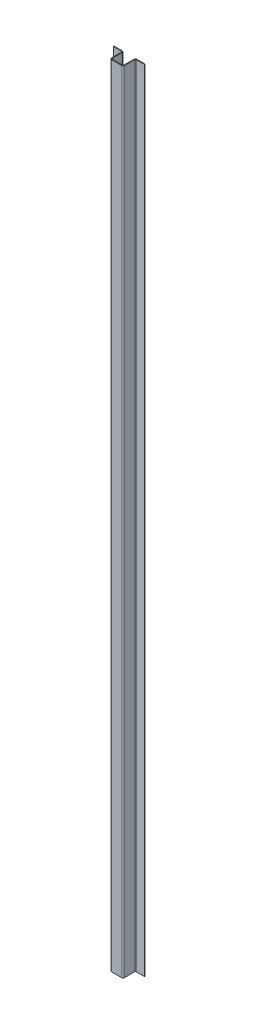
SolidWorks part; units mm, degrees
note: The reader was unsure of these and kept them because the rebuilt part matched: flange length of "Edge-Flange1", "Edge-Flange2".
material "Galvanized Steel"
ref_plane "Front Plane" through (0, 0, 0) normal (0, 0, 1) x (1, 0, 0)
ref_plane "Top Plane" through (0, 0, 0) normal (0, 1, 0) x (1, 0, 0)
ref_plane "Right Plane" through (0, 0, 0) normal (1, 0, 0) x (0, 0, -1)
sketch "Sketch1" plane through (0, 0, 0) normal (0, 0, 1) x (1, 0, 0)
  line L1 (20, -1214) -> (-20, -1214)
  line L2 (20, -1214) -> (20, 1214)
  line L3 (20, 1214) -> (-20, 1214)
  line L4 (-20, -1214) -> (-20, 1214)
  line L5 (20, -1214) -> (-20, 1214) construction
  line L6 (20, 1214) -> (-20, -1214) construction
  point P0 (0, 0)
  dimension "D1" = 2428
  dimension "D2" = 40
base flange "Base-Flange1" sketch "Sketch1" thickness 2 reverse thickness direction no parameters "D1"=8
edge flange "Edge-Flange1" sketch "Sketch10" flange profiles "Sketch10", "Sketch11" flange angle 90 flange length 40 flange position material inside bend radius 2.5 thickness 2 relief rectangular parameters "D6"=10, "D8"=1
sketch "Sketch10" plane through (20, 0, -2) normal (1, 0, 0) x (0, -1, 0)
  line L0 (1214, 0) -> (-1214, 0) construction
  line L1 (1214, 0) -> (-1214, 0)
  line L2 (-1214, 0) -> (-1214, 38)
  line L3 (-1214, 38) -> (1214, 38)
  line L4 (1214, 38) -> (1214, 0)
sketch "Sketch11" plane through (-20, 0, -2) normal (-1, 0, 0) x (0, 1, 0)
  line L0 (1214, 0) -> (-1214, 0) construction
  line L1 (1214, 0) -> (-1214, 0)
  line L2 (-1214, 0) -> (-1214, 38)
  line L3 (-1214, 38) -> (1214, 38)
  line L4 (1214, 38) -> (1214, 0)
bend "EdgeBend1" bend radius 2.5 bend angle 90 parameters "D5"=1
bend "EdgeBend2" bend radius 2.5 bend angle 90 parameters "D5"=2
edge flange "Edge-Flange2" sketch "Sketch16" flange profiles "Sketch16", "Sketch17" flange angle 90 flange length 30 flange position material inside bend radius 2.5 thickness 2 relief rectangular parameters "D6"=10, "D8"=1
sketch "Sketch16" plane through (-20, 0, -40) normal (0, 0, -1) x (0, -1, 0)
  line L2 (-1214, 0) -> (-1214, 28)
  line L3 (-1214, 28) -> (1214, 28)
  line L4 (1214, 28) -> (1214, 0)
  line L7 (-1214, 0) -> (1214, 0) construction
  line L8 (-1214, 0) -> (1214, 0)
sketch "Sketch17" plane through (20, 0, -40) normal (0, 0, -1) x (0, 1, 0)
  line L0 (-1214, 0) -> (1214, 0) construction
  line L1 (-1214, 0) -> (1214, 0)
  line L2 (-1214, 0) -> (-1214, 28)
  line L3 (-1214, 28) -> (1214, 28)
  line L4 (1214, 28) -> (1214, 0)
bend "EdgeBend3" bend radius 2.5 bend angle 90 parameters "D5"=3
bend "EdgeBend4" bend radius 2.5 bend angle 90 parameters "D5"=4
sketch "Bend-Lines1" [suppressed] plane through (0, 0, 0) normal (0, 1, 0) x (1, 0, 0)
sketch "Bounding-Box1" [suppressed] plane through (0, 0, 0) normal (0, 1, 0) x (1, 0, 0)
sheet metal parameters "Sheet-Metal8" thickness 2 parameters "D1"=8
flat pattern "Flat-Pattern8" [suppressed]
sketch "Bend-Lines2" plane through (0, 0, 0) normal (0, 1, 0) x (1, 0, 0)
sketch3d "Bounding-Box2" [suppressed]
  line L0 (-20, 1200, 0) -> (-20, -1200, 0) construction
  line L1 (20, 1200, 0) -> (20, -1200, 0) construction
  line L2 (-20, 1200, 0) -> (20, 1200, 0) construction
  line L3 (-20, -1200, 0) -> (20, -1200, 0) construction
sheet metal parameters "Sheet-Metal9" thickness 2 parameters "D1"=8
flat pattern "Flat-Pattern8"
sketch "Bend-Lines2" plane through (0, 0, 0) normal (0, 0, 1) x (1, 0, 0)
  line L0 (-18.2489, 1200) -> (-18.2489, -1200) construction
  line L1 (18.2489, -1200) -> (18.2489, 1200) construction
  line L2 (-18.2489, 1200) -> (-18.2489, -1200) construction
  line L3 (18.2489, -1200) -> (18.2489, 1200) construction
sketch3d "Bounding-Box2" [suppressed]
  line L0 (56.4978, 1200, 0) -> (56.4978, -1200, 0) construction
  line L1 (-56.4978, 1200, 0) -> (-56.4978, -1200, 0) construction
  line L2 (56.4978, 1200, 0) -> (-56.4978, 1200, 0) construction
  line L3 (56.4978, -1200, 0) -> (-56.4978, -1200, 0) construction
bend of the flat pattern "Flatten-<EdgeBend1>1"
bend of the flat pattern "Flatten-<EdgeBend2>1"
sheet metal parameters "Sheet-Metal10" thickness 2 parameters "D1"=8
flat pattern "Flat-Pattern8"
sketch "Bend-Lines2" plane through (0, 0, 0) normal (0, 0, 1) x (1, 0, 0)
  line L0 (-18.2489, 1214) -> (-18.2489, -1214) construction
  line L1 (18.2489, -1214) -> (18.2489, 1214) construction
  line L2 (-18.2489, 1214) -> (-18.2489, -1214) construction
  line L3 (18.2489, -1214) -> (18.2489, 1214) construction
  line L4 (54.7467, -1214) -> (54.7467, 1214) construction
  line L5 (-54.7467, 1214) -> (-54.7467, -1214) construction
  line L6 (54.7467, -1214) -> (54.7467, 1214) construction
  line L7 (-54.7467, 1214) -> (-54.7467, -1214) construction
sketch3d "Bounding-Box2" [suppressed]
  line L0 (82.9956, 1214, 0) -> (82.9956, -1214, 0) construction
  line L1 (-82.9956, 1214, 0) -> (-82.9956, -1214, 0) construction
  line L2 (82.9956, 1214, 0) -> (-82.9956, 1214, 0) construction
  line L3 (82.9956, -1214, 0) -> (-82.9956, -1214, 0) construction
bend of the flat pattern "Flatten-<EdgeBend1>1"
bend of the flat pattern "Flatten-<EdgeBend2>1"
bend of the flat pattern "Flatten-<EdgeBend3>1"
bend of the flat pattern "Flatten-<EdgeBend4>1"
